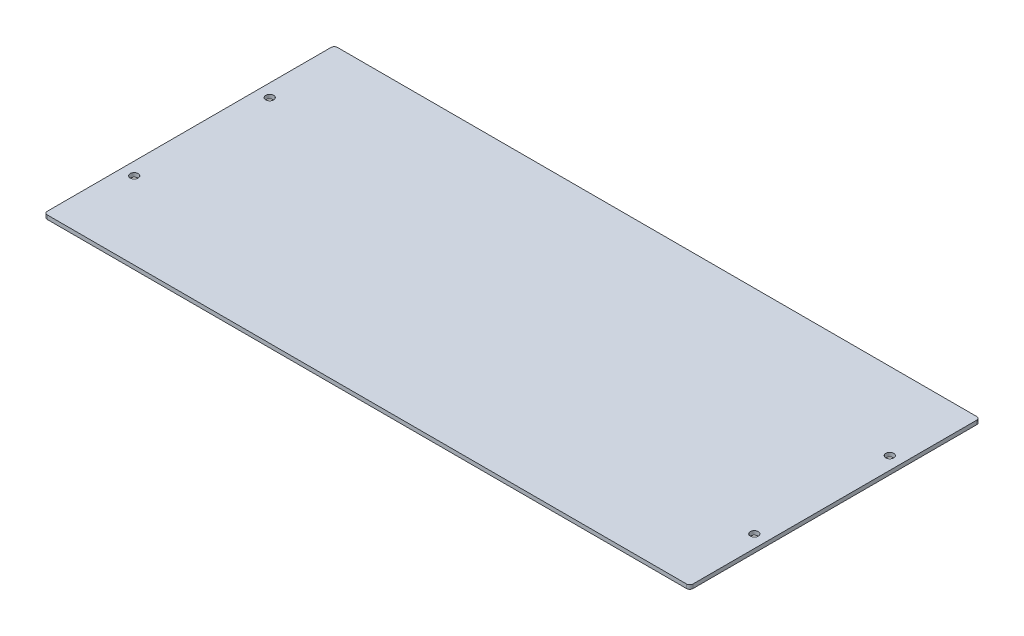
SolidWorks part; units mm, degrees
material "PE High Density"
ref_plane "Front Plane" through (0, 0, 0) normal (0, 0, 1) x (1, 0, 0)
ref_plane "Top Plane" through (0, 0, 0) normal (0, 1, 0) x (1, 0, 0)
ref_plane "Right Plane" through (0, 0, 0) normal (1, 0, 0) x (0, 0, -1)
sketch "Sketch1" plane through (0, 0, 0) normal (0, 1, 0) x (1, 0, 0)
  line L1 (-257.175, -115.57) -> (257.175, -115.57)
  line L2 (-257.175, -115.57) -> (-257.175, 115.57)
  line L3 (-257.175, 115.57) -> (257.175, 115.57)
  line L4 (257.175, -115.57) -> (257.175, 115.57)
  line L5 (-257.175, -115.57) -> (257.175, 115.57) construction
  line L6 (-257.175, 115.57) -> (257.175, -115.57) construction
  point P0 (0, 0)
  dimension "D1" = 514.35
  dimension "D2" = 231.14
extrude "Boss-Extrude1" add sketch "Sketch1" along normal blind 3.175
hole_wizard "1/4 (0.25) Diameter Hole1" positions "Sketch2" profile "Sketch3" hole size "1/4" standard "ANSI Inch" end condition through all
sketch "Sketch2" plane through (0, 3.175, 0) normal (0, 1, 0) x (1, 0, 0)
  line L0 (0, 115.57) -> (0, -115.57) construction
  line L1 (257.175, 115.57) -> (-257.175, 115.57) construction
  line L2 (-257.175, -115.57) -> (257.175, -115.57) construction
  line L3 (-257.175, 0) -> (257.175, 0) construction
  line L4 (-257.175, 115.57) -> (-257.175, -115.57) construction
  line L5 (257.175, -115.57) -> (257.175, 115.57) construction
  point P0 (-247.015, 53.975)
  point P17 (-247.015, -53.975)
  point P19 (247.015, -53.975)
  point P20 (247.015, 53.975)
  dimension "D1" = 107.95
  dimension "D2" = 10.16
sketch "Sketch3" plane through (-247.015, 3.175, -53.975) normal (1, 0, 0) x (0, 0, 1)
  line L0 (0, 0) -> (0, 3.175)
  line L1 (0, 3.175) -> (3.175, 3.175)
  line L2 (3.175, 3.175) -> (3.175, 0)
  line L5 (3.175, 0) -> (0, 0)
  line L11 (0, -6.35) -> (0, 107.95) construction
  dimension "Thru Hole Dia." = 6.35
  dimension "Thru Hole Depth" = 3.175
fillet "Fillet1" radius 2.54 4 edges at (257.175, 1.5875, 115.57) (-257.175, 1.5875, -115.57) (257.175, 1.5875, -115.57) (-257.175, 1.5875, 115.57)
